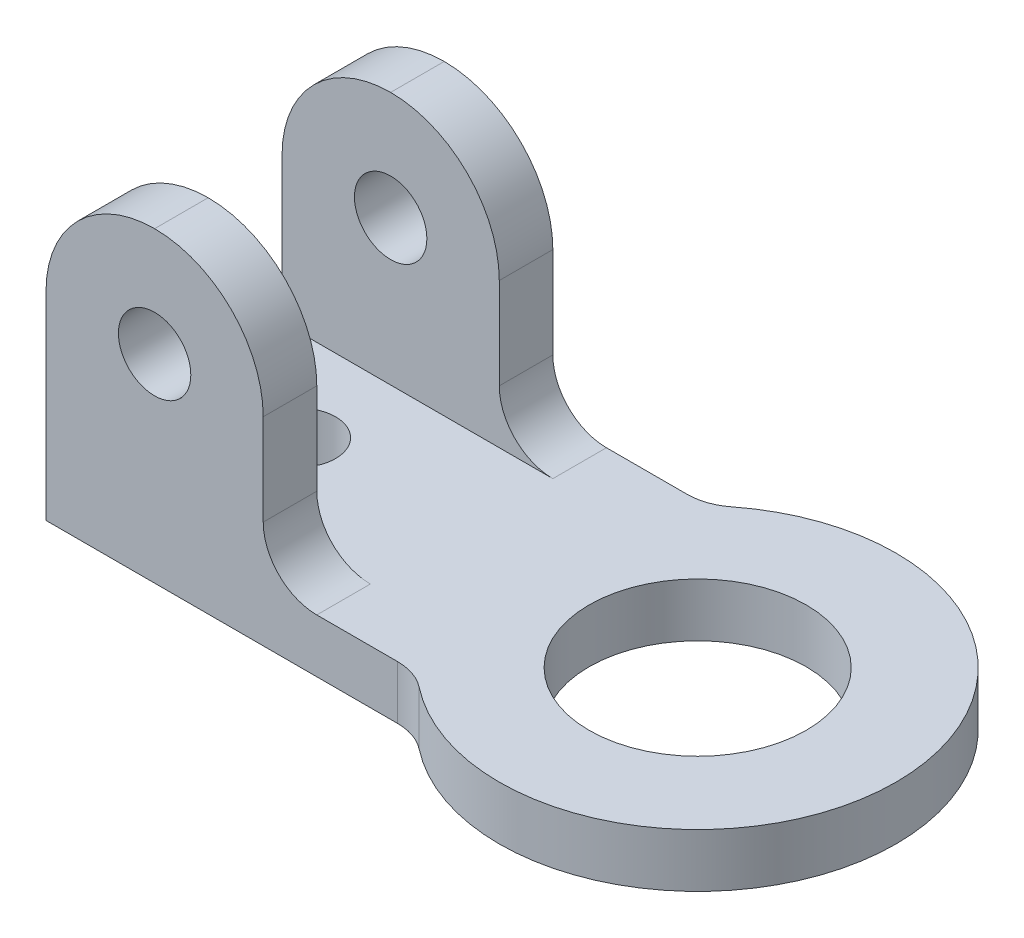
SolidWorks part; units mm, degrees
ref_plane "Front Plane" through (0, 0, 0) normal (0, 0, 1) x (1, 0, 0)
ref_plane "Top Plane" through (0, 0, 0) normal (0, 1, 0) x (1, 0, 0)
ref_plane "Right Plane" through (0, 0, 0) normal (1, 0, 0) x (0, 0, -1)
sketch "Sketch1" plane through (0, 0, 0) normal (0, 1, 0) x (1, 0, 0)
  line L0 (0, 0) -> (-88.9, 0) construction
  line L1 (-23.7853, 25.4) -> (-88.9, 25.4)
  line L2 (-23.7853, -25.4) -> (-88.9, -25.4)
  line L3 (0, 25.4) -> (-88.9, 25.4) construction
  line L4 (0, -25.4) -> (-88.9, -25.4) construction
  line L5 (-88.9, 25.4) -> (-88.9, -25.4)
  circle A0 centre (0, 0) radius 19.05
  arc A1 (-23.7853, -25.4) -> (-23.7853, 25.4) centre (0, 0) ccw
  circle A2 centre (-69.85, 0) radius 6.35
  dimension "D1" = 38.1
  dimension "D2" = 69.596
  dimension "D6" = 12.7
  dimension "D3" = 88.9
  dimension "D4" = 25.4
  dimension "D7" = 19.05
  dimension "D5" = 25.4
extrude "Boss-Extrude1" add sketch "Sketch1" along normal blind 9.398
sketch "Sketch4" plane through (0, 9.398, 0) normal (0, 1, 0) x (1, 0, 0)
  line L0 (0, 0) -> (-88.9, 0) construction
  line L1 (-88.9, 25.4) -> (-50.8, 25.4)
  line L2 (-88.9, 25.4) -> (-88.9, 16.002)
  line L3 (-88.9, 16.002) -> (-50.8, 16.002)
  line L4 (-50.8, 25.4) -> (-50.8, 16.002)
  line L5 (-88.9, 25.4) -> (-88.9, -25.4) construction
  line L6 (-50.8, -25.4) -> (-50.8, -16.002)
  line L7 (-88.9, -16.002) -> (-50.8, -16.002)
  line L8 (-88.9, -25.4) -> (-88.9, -16.002)
  line L9 (-88.9, -25.4) -> (-50.8, -25.4)
  dimension "D1" = 9.398
  dimension "D2" = 38.1
extrude "Boss-Extrude3" add sketch "Sketch4" along normal blind 44.45
fillet "Fillet1" radius 19.05 4 edges at (-88.9, 53.848, 20.701) (-88.9, 53.848, -20.701) (-50.8, 53.848, -20.701) (-50.8, 53.848, 20.701)
fillet "Fillet2" radius 9.398 4 edges at (-23.7853, 4.699, 25.4) (-23.7853, 4.699, -25.4) (-50.8, 9.398, 20.701)
sketch "Sketch6" plane through (0, 0, 25.4) normal (0, 0, 1) x (1, 0, 0)
  circle A0 centre (-69.85, 34.798) radius 6.35
  dimension "D1" = 12.7
extrude "Cut-Extrude1" cut sketch "Sketch6" against normal up to surface (50.8 mm away) up to face at (-55.0018, 21.8727, -25.4)
